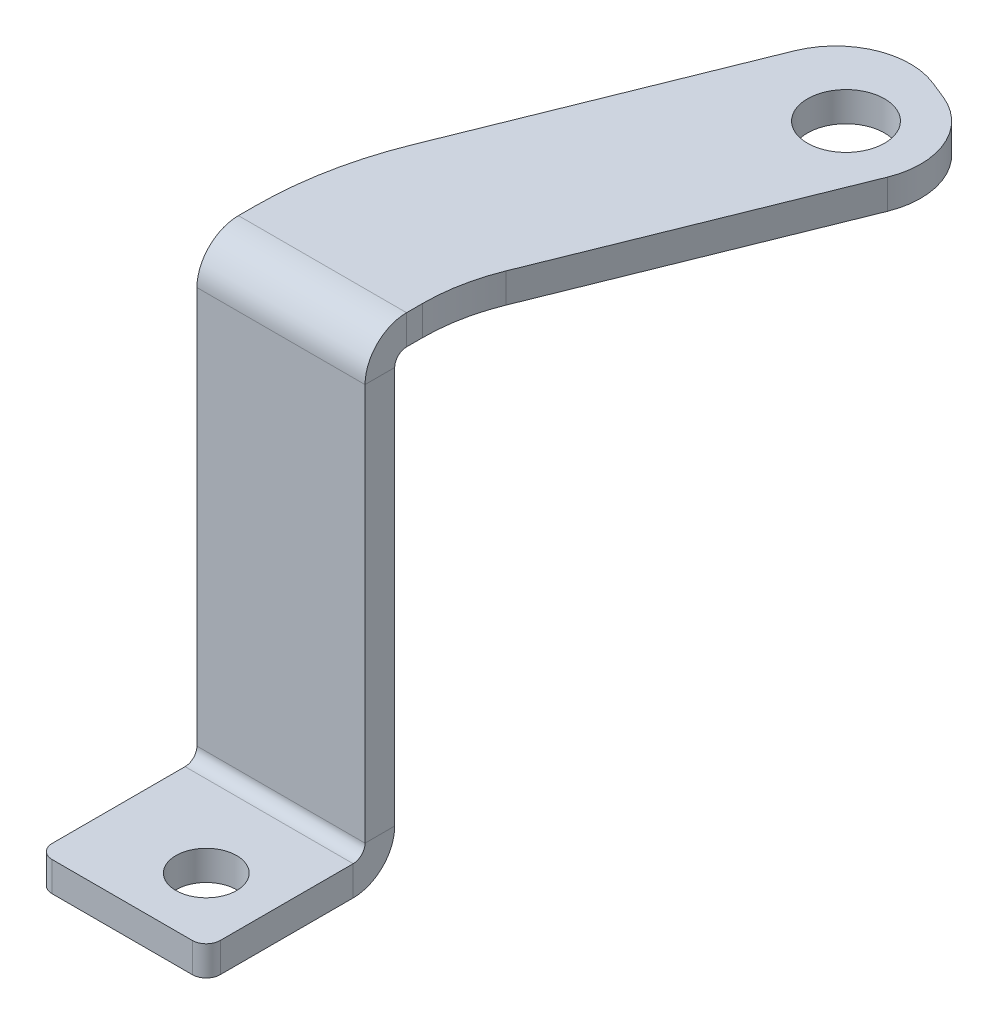
SolidWorks part; units mm, degrees
note: The reader was unsure of these and kept them because the rebuilt part matched: flange length of "Edge-Flange1", "Edge-Flange2"; thickness of "Edge-Flange1", "Edge-Flange2".
material "Copper"
ref_plane "Front Plane" through (0, 0, 0) normal (0, 0, 1) x (1, 0, 0)
ref_plane "Top Plane" through (0, 0, 0) normal (0, 1, 0) x (1, 0, 0)
ref_plane "Right Plane" through (0, 0, 0) normal (1, 0, 0) x (0, 0, -1)
sketch "Sketch1" plane through (0, 0, 0) normal (0, 1, 0) x (1, 0, 0)
  line L1 (7, -5.5) -> (7, 10)
  line L2 (7, 10) -> (-11, 10)
  line L3 (5.5, -7) -> (-9.5, -7)
  line L4 (-11, -5.5) -> (-11, 10)
  arc A1 (5.5, -7) -> (7, -5.5) centre (5.5, -5.5) ccw
  arc A2 (-9.5, -7) -> (-11, -5.5) centre (-9.5, -5.5) cw
  circle A3 centre (0, 0) radius 3.25
  point P3 (7.7269, -0.0376)
  point P5 (0, 0)
  dimension "D1" = 6.5
  dimension "D2" = 1.5
  dimension "D4" = 18
  dimension "D3" = 10
  dimension "D5" = 7
  dimension "D6" = 7
base flange "Base-Flange1" sketch "Sketch1" thickness 3.175 reverse thickness direction no parameters "D1"=1.27
edge flange "Edge-Flange1" sketch "Sketch8" flange angle 90 flange length 48.2375 flange position material outside bend radius 1.27 thickness 3.175 relief rectangular parameters "D1"=0.7366, "D6"=10
sketch "Sketch8" plane through (0, 0, -10) normal (0, 0, -1) x (-1, 0, 0)
  line L0 (-7, 0) -> (11, 0) construction
  line L1 (-7, 0) -> (11, 0)
  line L2 (-7, 0) -> (-7, 45.0625)
  line L3 (-7, 45.0625) -> (11, 45.0625)
  line L4 (11, 45.0625) -> (11, 0)
  line L5 (-5.25, 45.0625) -> (-20.25, 45.0625) construction
bend "EdgeBend1" bend radius 1.27 bend angle 90 parameters "D5"=1
edge flange "Edge-Flange2" sketch "Sketch11" flange angle 90 flange length 6.175 flange position material outside bend radius 1.27 thickness 3.175 relief rectangular parameters "D1"=0.7366, "D6"=10
sketch "Sketch11" plane through (0, 45.0625, -13.175) normal (0, 1, 0) x (1, 0, 0)
  line L0 (-11, 0) -> (7, 0) construction
  line L1 (-11, 0) -> (7, 0)
  line L2 (-11, 0) -> (-11, 3)
  line L4 (7, 3) -> (7, 0)
  line L7 (-11, 3) -> (7, 3)
  dimension "D1" = 3
bend "EdgeBend2" bend radius 1.27 bend angle 90 parameters "D5"=2
sketch "Sketch12" plane through (0, 48.2375, 0) normal (0, 1, 0) x (1, 0, 0)
  line L0 (7, 16.175) -> (-11, 16.175)
  line L1 (-8.2499, 30.368) -> (3.4737, 59.485)
  line L2 (20.171, 52.762) -> (8.4474, 23.645)
  line L3 (7, 14.445) -> (7, 16.175) construction
  line L4 (-11, 16.175) -> (-11, 14.445) construction
  line L5 (15.738, 63.171) -> (13.8827, 63.918)
  arc A0 (-11, 16.175) -> (-8.2499, 30.368) centre (27, 16.175) cw
  arc A2 (8.4474, 23.645) -> (7, 16.175) centre (27, 16.175) ccw
  arc A3 (20.171, 52.762) -> (15.738, 63.171) centre (12.75, 55.75) ccw
  circle A5 centre (12.75, 55.75) radius 4.125
  arc A6 (13.8827, 63.918) -> (3.4737, 59.485) centre (10.8947, 56.497) ccw
  dimension "D1" = 8.25
  dimension "D2" = 8
  dimension "D3" = 20
extrude "Boss-Extrude1" add sketch "Sketch12" against normal blind 3.175
sketch "Bend-Lines1" [suppressed] plane through (0, 0, 0) normal (0, 1, 0) x (1, 0, 0)
sketch "Bounding-Box1" [suppressed] plane through (0, 0, 0) normal (0, 1, 0) x (1, 0, 0)
sheet metal parameters "Sheet-Metal1" thickness 3.175 parameters "D1"=0.7366
flat pattern "Flat-Pattern1" [suppressed]
sketch "Bend-Lines2" plane through (0, 0, 0) normal (0, 1, 0) x (1, 0, 0)
sketch3d "Bounding-Box2" [suppressed]
  line L0 (7, 12.5, 0) -> (7, -7, 0) construction
  line L1 (-7, 12.5, 0) -> (-7, -7, 0) construction
  line L2 (7, 12.5, 0) -> (-7, 12.5, 0) construction
  line L3 (7, -7, 0) -> (-7, -7, 0) construction
sheet metal parameters "Sheet-Metal2" thickness 3.175 parameters "D1"=0.7366, "D7"=2
flat pattern "Flat-Pattern1"
sketch "Bend-Lines2" plane through (0, 0, 0) normal (0, 1, 0) x (1, 0, 0)
  line L0 (7, 13.1273) -> (-7, 13.1273) construction
  line L1 (7, 13.1273) -> (-7, 13.1273) construction
sketch3d "Bounding-Box2" [suppressed]
  line L0 (7, 56.8171, 0) -> (7, -7, 0) construction
  line L1 (-7, 56.8171, 0) -> (-7, -7, 0) construction
  line L2 (7, 56.8171, 0) -> (-7, 56.8171, 0) construction
  line L3 (7, -7, 0) -> (-7, -7, 0) construction
bend of the flat pattern "Flatten-<EdgeBend1>1"
sheet metal parameters "Sheet-Metal3" thickness 3.175 parameters "D1"=0.7366, "D7"=2
flat pattern "Flat-Pattern1"
sketch "Bend-Lines2" plane through (0, 0, 0) normal (0, 1, 0) x (1, 0, 0)
  line L0 (7, 13.1273) -> (-7, 13.1273) construction
  line L1 (7, 13.1273) -> (-7, 13.1273) construction
  line L2 (7, 57.4445) -> (-7, 57.4445) construction
  line L3 (7, 57.4445) -> (-7, 57.4445) construction
sketch3d "Bounding-Box2" [suppressed]
  line L0 (7, 61.0718, 0) -> (7, -7, 0) construction
  line L1 (-7, 61.0718, 0) -> (-7, -7, 0) construction
  line L2 (7, 61.0718, 0) -> (-7, 61.0718, 0) construction
  line L3 (7, -7, 0) -> (-7, -7, 0) construction
bend of the flat pattern "Flatten-<EdgeBend1>1"
bend of the flat pattern "Flatten-<EdgeBend2>1"
sheet metal parameters "Sheet-Metal4" thickness 3.175 parameters "D1"=0.7366, "D7"=2
flat pattern "Flat-Pattern1"
sketch "Bend-Lines2" plane through (0, 0, 0) normal (0, 1, 0) x (1, 0, 0)
  line L0 (7, 10.5753) -> (-11, 10.5753) construction
  line L1 (7, 10.5753) -> (-11, 10.5753) construction
  line L2 (7, 56.7884) -> (-11, 56.7884) construction
  line L3 (7, 56.7884) -> (-11, 56.7884) construction
sketch3d "Bounding-Box2" [suppressed]
  line L0 (16.2858, 112.8279, 0) -> (1.0393, -3.6124, 0) construction
  line L1 (-10.2205, 116.2986, 0) -> (-25.467, -0.1417, 0) construction
  line L2 (16.2858, 112.8279, 0) -> (-10.2205, 116.2986, 0) construction
  line L3 (1.0393, -3.6124, 0) -> (-25.467, -0.1417, 0) construction
bend of the flat pattern "Flatten-<EdgeBend1>1"
bend of the flat pattern "Flatten-<EdgeBend2>1"
